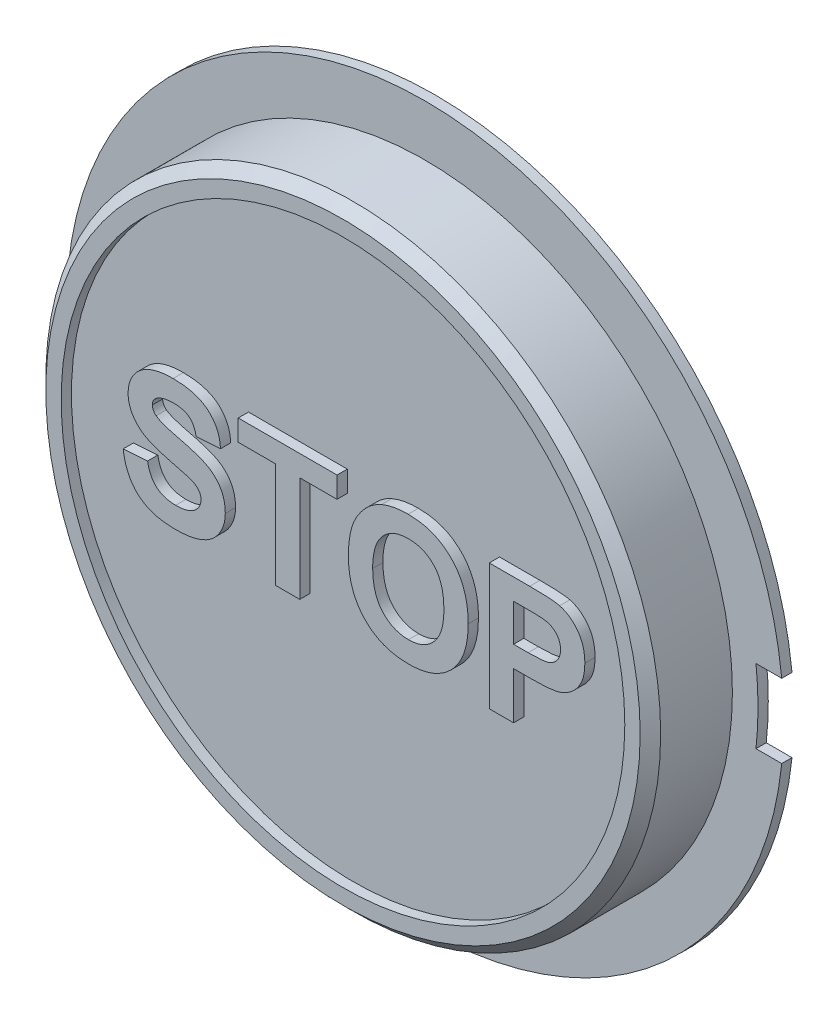
SolidWorks part; units mm, degrees
ref_plane "Plan de face" through (0, 0, 0) normal (0, 0, 1) x (1, 0, 0)
ref_plane "Plan de dessus" through (0, 0, 0) normal (0, 1, 0) x (1, 0, 0)
ref_plane "Plan de droite" through (0, 0, 0) normal (1, 0, 0) x (0, 0, -1)
sketch "Esquisse1" plane through (0, 0, 0) normal (0, 0, 1) x (1, 0, 0)
  circle A0 centre (0, 0) radius 30
  dimension "D1" = 60
extrude "Boss.-Extru.1" add sketch "Esquisse1" along normal blind 7
sketch "Esquisse2" plane through (0, 0, 7) normal (0, 0, 1) x (1, 0, 0)
  circle A0 centre (0, 0) radius 30
  circle A1 centre (0, 0) radius 27.5
  circle A2 centre (0, 0) radius 30 construction
  point P9 (-20.3153, 4.7944)
  point P10 (0, 0)
  point P11 (-20.3153, 3.3717)
  point P12 (-20.1256, 3.9408)
  point P14 (0, 0)
  dimension "D1" = 2.5
extrude "Boss.-Extru.3" add sketch "Esquisse2" along normal blind 1
sketch "Esquisse3" plane through (0, 0, 7) normal (0, 0, 1) x (1, 0, 0)
  text T0 "STOP" font "Arial" height in points 48
extrude "Boss.-Extru.4" add sketch "Esquisse3" along normal blind 1
sketch "Esquisse4" plane through (0, 0, 0) normal (0, 0, -1) x (-1, 0, 0)
  line L0 (30, 0) -> (-30, 0) construction
  line L1 (-32.3, 3.6) -> (-34.8144, 3.6)
  line L2 (32.3, 3.6) -> (34.8144, 3.6)
  line L3 (34.8144, -3.6) -> (32.3, -3.6)
  line L5 (-32.3, -3.6) -> (-34.8144, -3.6)
  arc A0 (34.8144, 3.6) -> (-34.8144, 3.6) centre (0, 0) ccw
  circle A1 centre (0, 0) radius 30 construction
  arc A3 (-34.8144, -3.6) -> (34.8144, -3.6) centre (0, 0) ccw
  arc A4 (-32.3, 3.6) -> (-32.3, -3.6) centre (0, 0) ccw
  arc A5 (32.3, -3.6) -> (32.3, 3.6) centre (0, 0) ccw
  point P0 (0, 0)
  point P6 (0, 0)
  point P8 (-32.7658, 2.5533)
  point P13 (0, 0)
  point P14 (-0.6287, -0.5706)
  point P18 (28.6891, 8.7712)
  point P19 (0, 0)
  point P22 (32.5, 0)
  dimension "D1" = 70
  dimension "D2" = 7.2
  dimension "D3" = 3.6
  dimension "D4" = 2.5
extrude "Boss.-Extru.5" add sketch "Esquisse4" along normal blind 1
sketch "Esquisse5" plane through (0, 0, -1) normal (0, 0, -1) x (-1, 0, 0)
  circle A0 centre (0, 0) radius 28.5
  circle A1 centre (0, 0) radius 19
  dimension "D1" = 57
  dimension "D2" = 38
extrude "Boss.-Extru.6" add sketch "Esquisse5" along normal blind 1.75
chamfer "Chanfrein1" distance 1.75 angle 45 1 edges at (-19, 0, -1)
chamfer "Chanfrein2" distance 1 angle 45 1 edges at (30, 0, 8)
equation "\"D3@Esquisse4\"=\"D2@Esquisse4\"/2"
